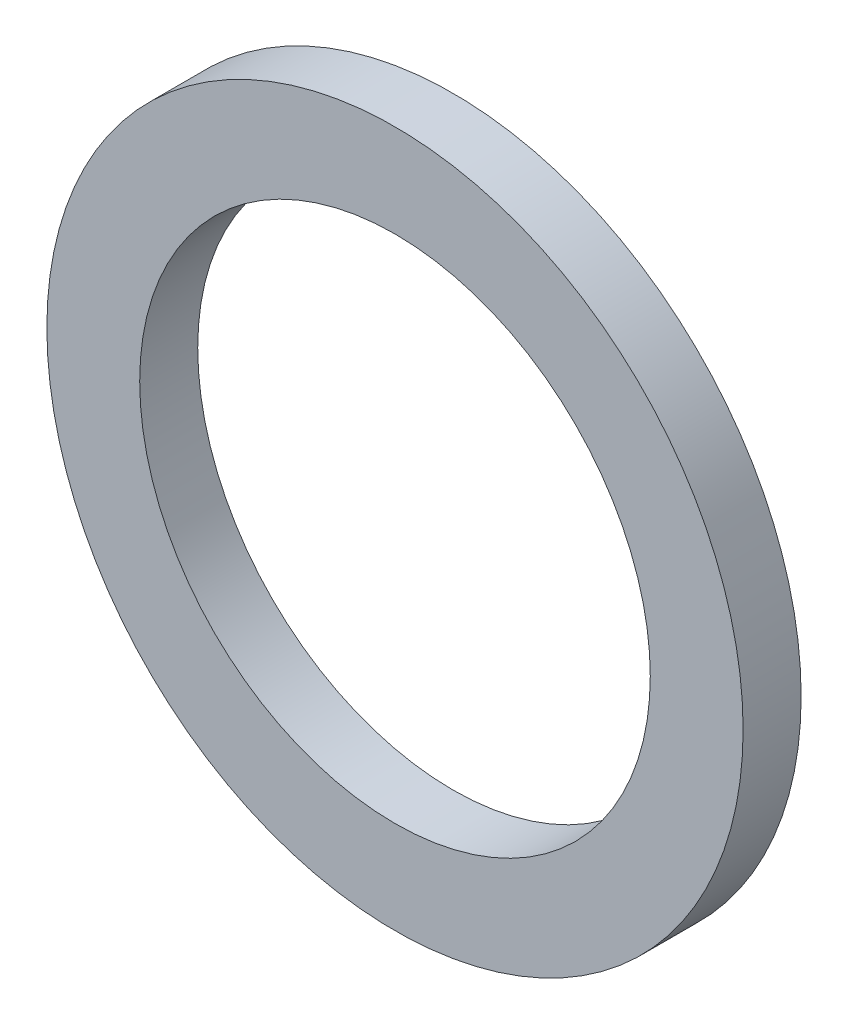
SolidWorks part; units mm, degrees
ref_plane "Front Plane" through (0, 0, 0) normal (0, 0, 1) x (1, 0, 0)
ref_plane "Top Plane" through (0, 0, 0) normal (0, 1, 0) x (1, 0, 0)
ref_plane "Right Plane" through (0, 0, 0) normal (1, 0, 0) x (0, 0, -1)
sketch "Sketch1" plane through (0, 0, 0) normal (0, 0, 1) x (1, 0, 0)
  circle A0 centre (0, 0) radius 30
  circle A1 centre (0, 0) radius 22
  dimension "D1" = 8
  dimension "D2" = 60
extrude "Spring Outer Ring" add sketch "Sketch1" along normal mid plane 5
sketch "Sketch3" plane through (0, 0, 0) normal (0, 0, 1) x (1, 0, 0)
  line L0 (0, 22) -> (0, 30) construction
  circle A0 centre (-26, 0) radius 1.9176
  circle A1 centre (0, 0) radius 22 construction
  circle A2 centre (0, 0) radius 30 construction
  circle A3 centre (0, 0) radius 26 construction
  point P12 (0, 26)
  point P13 (-25.9565, 1.5036)
  dimension "D1" = 3.8352
equation "\"n\" = 1'Number of twists in spring"
